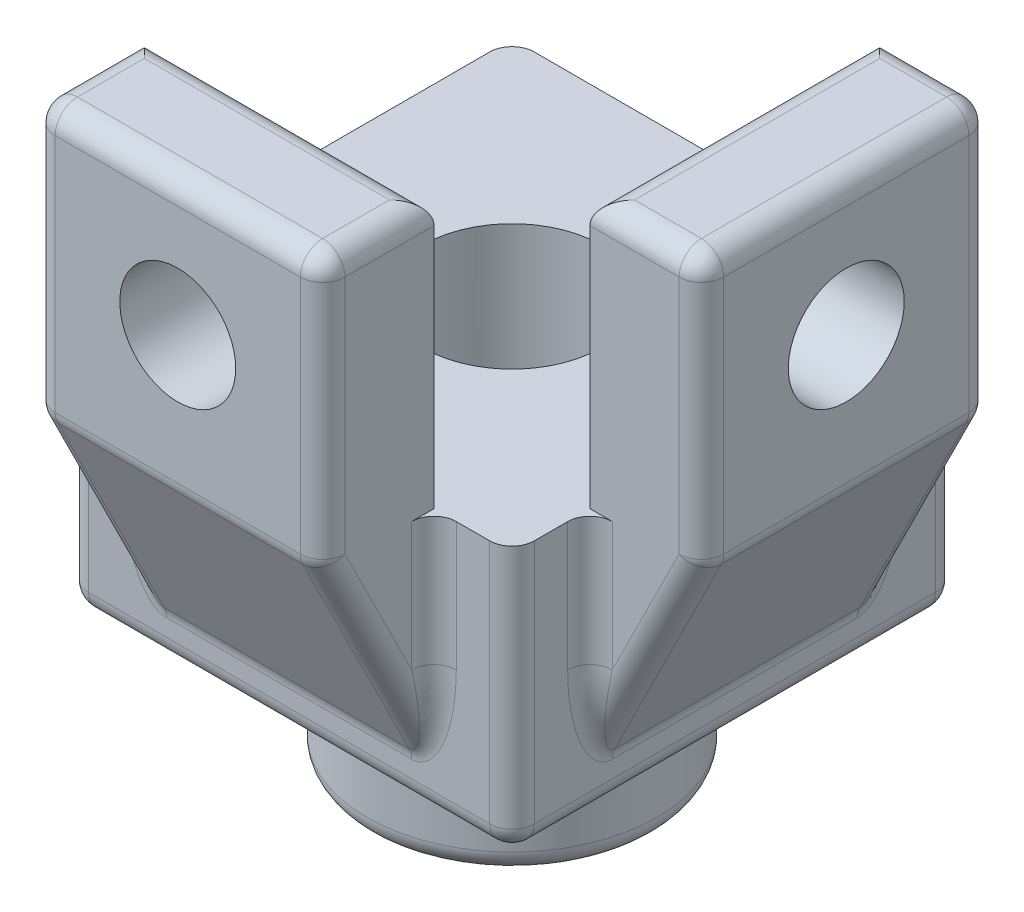
SolidWorks part; units mm, degrees
ref_plane "前视基准面" through (0, 0, 0) normal (0, 0, 1) x (1, 0, 0)
ref_plane "上视基准面" through (0, 0, 0) normal (0, 1, 0) x (1, 0, 0)
ref_plane "右视基准面" through (0, 0, 0) normal (1, 0, 0) x (0, 0, -1)
sketch "草图1" plane through (0, 0, 0) normal (0, 1, 0) x (1, 0, 0)
  line L0 (24.7644, 18.8625) -> (44.7644, 18.8625)
  line L1 (44.7644, 18.8625) -> (44.7644, 38.8625)
  line L2 (44.7644, 38.8625) -> (24.7644, 38.8625)
  line L3 (24.7644, 38.8625) -> (24.7644, 18.8625)
extrude "凸台-拉伸1" add sketch "草图1" along normal blind 12
sketch "草图2" plane through (0, 0, 0) normal (0, -1, 0) x (1, 0, 0)
  circle A0 centre (34.7644, -28.8625) radius 6.5
extrude "凸台-拉伸2" add sketch "草图2" along normal blind 6
sketch "草图3" plane through (44.7644, 0, 0) normal (1, 0, 0) x (0, 0, -1)
  line L1 (18.8625, 12) -> (38.8625, 12) construction
  line L2 (22.3625, 12) -> (22.3625, 2)
  line L5 (35.3625, 2) -> (35.3625, 24)
  line L6 (35.3625, 24) -> (22.3625, 24)
  line L7 (22.3625, 24) -> (22.3625, 12)
  line L8 (22.3625, 2) -> (35.3625, 2)
extrude "凸台-拉伸3" add sketch "草图3" along normal blind 5
sketch "草图4" plane through (0, 0, -22.3625) normal (0, 0, 1) x (1, 0, 0)
  line L4 (49.7644, 12) -> (44.7644, 2)
  line L5 (49.7644, 24) -> (49.7644, 2) construction
  line L6 (44.7644, 2) -> (49.7644, 2)
  line L7 (49.7644, 2) -> (49.7644, 12)
extrude "切除-拉伸1" cut sketch "草图4" against normal through all
sketch "草图5" plane through (0, 0, -18.8625) normal (0, 0, 1) x (1, 0, 0)
  line L1 (24.7644, 12) -> (44.7644, 12) construction
  line L2 (28.2644, 12) -> (28.2644, 2)
  line L6 (41.2644, 2) -> (41.2644, 24)
  line L7 (41.2644, 24) -> (28.2644, 24)
  line L8 (28.2644, 24) -> (28.2644, 12)
  line L9 (41.2644, 2) -> (28.2644, 2)
extrude "凸台-拉伸4" add sketch "草图5" along normal blind 5
sketch "草图6" plane through (41.2644, 0, 0) normal (1, 0, 0) x (0, 0, -1)
  line L4 (13.8625, 12) -> (13.8625, 2)
  line L5 (13.8625, 2) -> (13.8625, 24) construction
  line L6 (13.8625, 2) -> (18.8625, 2)
  line L7 (18.8625, 2) -> (13.8625, 12)
extrude "切除-拉伸2" cut sketch "草图6" against normal through all
sketch "草图7" plane through (0, -6, 0) normal (0, -1, 0) x (1, 0, 0)
  circle A0 centre (34.7644, -28.8625) radius 4
extrude "切除-拉伸3" cut sketch "草图7" against normal through all
sketch "草图8" plane through (49.7644, 0, 0) normal (1, 0, 0) x (0, 0, -1)
  circle A0 centre (28.8625, 18) radius 2.6
extrude "切除-拉伸4" cut sketch "草图8" against normal through all
sketch "草图9" plane through (0, 0, -13.8625) normal (0, 0, 1) x (1, 0, 0)
  circle A0 centre (34.7644, 18) radius 2.6
extrude "切除-拉伸5" cut sketch "草图9" against normal through all
fillet "圆角1" radius 1 2 edges at (34.7644, 0, -35.3625) (34.7644, -6, -35.3625)
fillet "圆角4" radius 1 32 edges at (28.2644, 7, -18.8625) (41.2644, 7, -18.8625) (44.7644, 7, -35.3625) (44.7644, 7, -22.3625) (47.2644, 24, -35.3625) (49.7644, 24, -28.8625) (47.2644, 24, -22.3625) (44.7644, 24, -28.8625) (41.2644, 24, -16.3625) (34.7644, 24, -13.8625) (28.2644, 24, -16.3625) (34.7644, 24, -18.8625) (28.2644, 7, -16.3625) (34.7644, 12, -13.8625) (41.2644, 7, -16.3625) (34.7644, 2, -18.8625) (47.2644, 7, -35.3625) (44.7644, 2, -28.8625) (47.2644, 7, -22.3625) (49.7644, 12, -28.8625) (34.7644, 0, -18.8625) (44.7644, 0, -28.8625) (34.7644, 0, -38.8625) (24.7644, 0, -28.8625) (41.2644, 18, -13.8625) (28.2644, 18, -13.8625) (49.7644, 18, -22.3625) (49.7644, 18, -35.3625) (44.7644, 6, -38.8625) (24.7644, 6, -38.8625) (24.7644, 6, -18.8625) (44.7644, 6, -18.8625)
